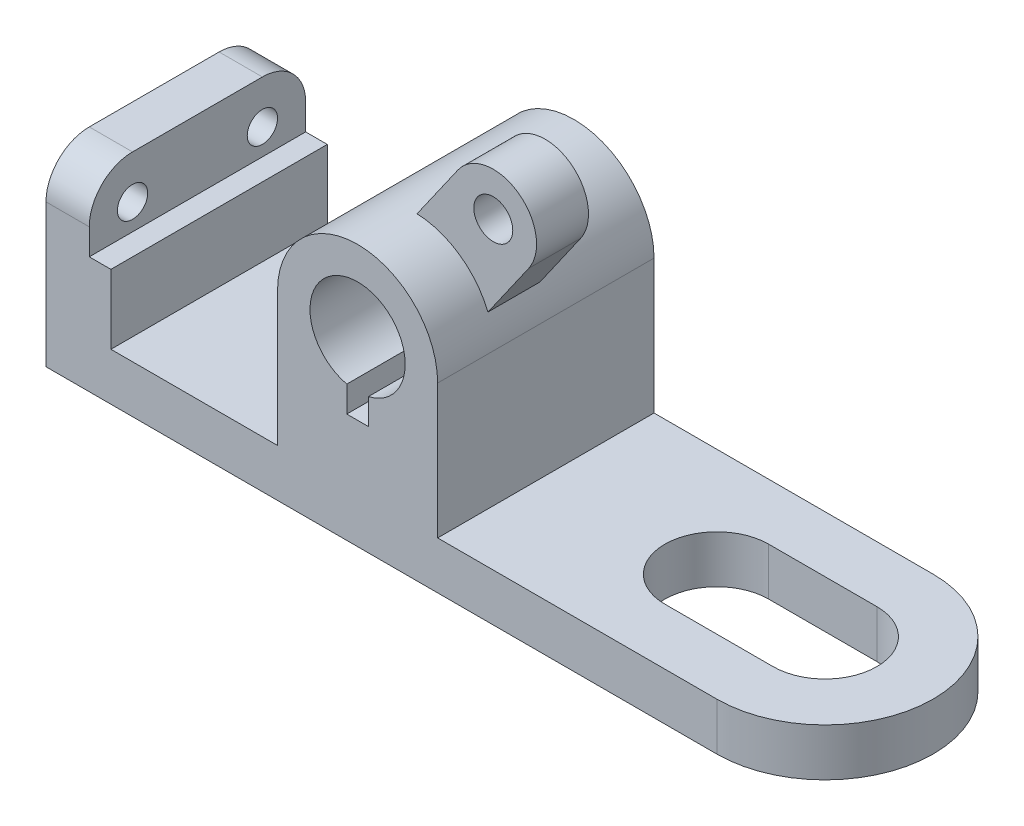
SolidWorks part; units mm, degrees
ref_plane "Front Plane" through (0, 0, 0) normal (0, 0, 1) x (1, 0, 0)
ref_plane "Top Plane" through (0, 0, 0) normal (0, 1, 0) x (1, 0, 0)
ref_plane "Right Plane" through (0, 0, 0) normal (1, 0, 0) x (0, 0, -1)
sketch "Sketch1" plane through (0, 0, 0) normal (0, 0, 1) x (1, 0, 0)
  line L0 (-72, 0) -> (-72, 43)
  line L1 (-72, 43) -> (-62, 43)
  line L2 (-62, 43) -> (-62, 27)
  line L3 (-62, 27) -> (-57, 27)
  line L4 (-57, 27) -> (-57, 11)
  line L5 (-57, 11) -> (-18.5, 11)
  line L6 (-18.5, 11) -> (-18.5, 42)
  line L7 (-72, 0) -> (108, 0)
  line L8 (108, 0) -> (108, 11)
  line L9 (108, 11) -> (18.5, 11)
  line L10 (18.5, 11) -> (18.5, 42)
  line L11 (0, 9.225) -> (0, -5.7497) construction
  line L12 (-2.5, 31.2879) -> (-2.5, 25.2879)
  line L13 (2.5, 31.2879) -> (2.5, 25.2879)
  line L14 (2.5, 25.2879) -> (-2.5, 25.2879)
  line L15 (0.7358, 60.4854) -> (10.1629, 73.9486)
  line L16 (17.1189, 49.0138) -> (26.546, 62.4771)
  line L17 (0, 42) -> (27.9758, 81.9535) construction
  arc A0 (2.5, 31.2879) -> (-2.5, 31.2879) centre (0, 42) ccw
  arc A1 (18.5, 42) -> (-18.5, 42) centre (0, 42) ccw
  arc A2 (26.546, 62.4771) -> (10.1629, 73.9486) centre (18.3544, 68.2129) ccw
  circle A3 centre (18.3544, 68.2129) radius 4.5
  point P18 (-67, 43)
  point P30 (0, 0)
  point P31 (22.3661, 60.3555)
  point P32 (8.6364, 71.7685)
  point P33 (0, 0)
  point P34 (0, 0)
  point P35 (0, 0)
  point P36 (0.725, 60.4858)
  point P37 (17.129, 48.9891)
  dimension "D3" = 37
  dimension "D4" = 22
  dimension "D14" = 20
  dimension "D15" = 9
  dimension "D1" = 11
  dimension "D2" = 42
  dimension "D5" = 16
  dimension "D6" = 43
  dimension "D7" = 72
  dimension "D8" = 5
  dimension "D9" = 15
  dimension "D10" = 180
  dimension "D11" = 5
  dimension "D12" = 6
  dimension "D13" = 55
  dimension "D16" = 32
extrude "Boss-Extrude1" add sketch "Sketch1" along normal mid plane 50 contours L10 A1 L6 L5 L4 L3 L2 L1 L0 L7 L8 L9 A0 L13 L14 L12 region at (2.5825, 16.8138, 0)
extrude "Boss-Extrude2" add sketch "Sketch1<3>" along normal blind 12 contours L16 A2 L15 A1 A3 region at (10.8417, 57.4835, 0)
sketch "Sketch1<3>" plane through (0, 0, 0) normal (0, 0, 1) x (1, 0, 0) same geometry as "Sketch1"
sketch "Sketch2" plane through (0, 11, 0) normal (0, 1, 0) x (1, 0, 0)
  line L0 (58, 0) -> (83, 0) construction
  line L1 (58, 12) -> (83, 12)
  line L2 (58, -12) -> (83, -12)
  line L3 (-72, -25) -> (-72, 25) construction
  line L4 (83, 28.4364) -> (83, -52.1966) construction
  arc A0 (58, 12) -> (58, -12) centre (58, 0) ccw
  arc A1 (83, -12) -> (83, 12) centre (83, 0) ccw
  arc A3 (83, -25) -> (83, 25) centre (83, 0) ccw
  point P3 (70.5, 0)
  line M3 (108, 25) -> (18.5, 25)
  line M5 (18.5, -25) -> (108, -25)
  line M6 (108, -25) -> (108, 25)
  dimension "D2" = 12
  dimension "D4" = 25
  dimension "D1" = 25
  dimension "D3" = 155
extrude "Cut-Extrude1" cut sketch "Sketch2" against normal up to next contours L2 A1 L1 A0 | A3 M6 M3 | A3 M5 M6 region at (70.5, 11, 0) region at (102.4158, 11, -19.4158) region at (102.4158, 11, 19.4158)
sketch "Sketch3" plane through (-72, 0, 0) normal (-1, 0, 0) x (0, 0, 1)
  line L0 (0, -2.6448) -> (0, 5.0291) construction
  line L1 (25, 0) -> (25, 43) construction
  line L2 (25, 43) -> (-25, 43) construction
  circle A0 centre (15, 33) radius 10
  circle A1 centre (15, 33) radius 3.5
  circle A2 centre (-15, 33) radius 3.5
  circle A3 centre (-15, 33) radius 10
  line M2 (-25, 43) -> (-25, 0)
  line M4 (25, 0) -> (25, 43)
  line M5 (25, 43) -> (-25, 43)
  dimension "D1" = 7
  dimension "D2" = 20
extrude "Cut-Extrude2" cut sketch "Sketch3" against normal up to next contours A1 | A0 M4 M5 | A2 | A3 M2 M5 region at (-72, 40.7663, -22.7663) region at (-72, 40.7663, 22.7663) region at (-72, 33, 15) region at (-72, 33, -15)
